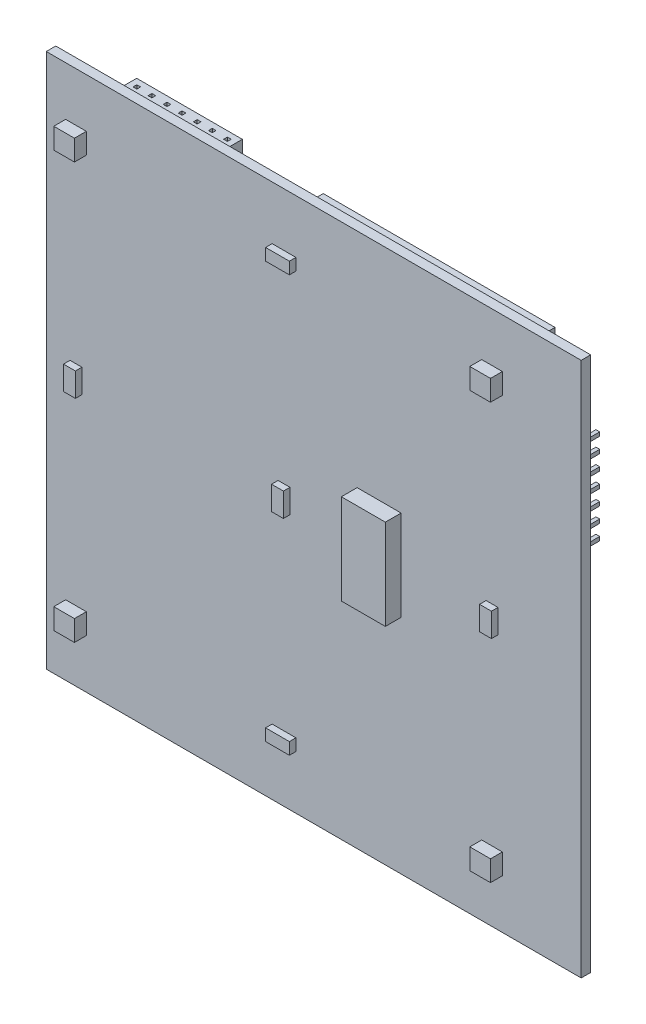
SolidWorks part; units mm, degrees
ref_plane "正面" through (0, 0, 0) normal (0, 0, 1) x (1, 0, 0)
ref_plane "平面" through (0, 0, 0) normal (0, 1, 0) x (1, 0, 0)
ref_plane "右側面" through (0, 0, 0) normal (1, 0, 0) x (0, 0, -1)
sketch "ｽｹｯﾁ1" plane through (0, 0, 0) normal (0, 0, 1) x (1, 0, 0)
  line L0 (-45, 0) -> (45, 0) construction
  line L1 (-45, 45) -> (45, 45)
  line L2 (-45, 45) -> (-45, -45)
  line L3 (-45, -45) -> (45, -45)
  line L4 (45, 45) -> (45, -45)
  line L5 (0, -45) -> (0, 45) construction
  point P8 (0, 0)
  dimension "D1" = 90
  dimension "D2" = 90
  dimension "D3" = 0
  dimension "D4" = 0
extrude "ﾎﾞｽ - 押し出し1" add sketch "ｽｹｯﾁ1" along normal blind 1.6
sketch "ｽｹｯﾁ4" plane through (0, 0, 0) normal (0, 0, -1) x (-1, 0, 0)
  line L0 (-45, -45) -> (-45, 45) construction
  line L1 (-23.89, -36.1) -> (-6.11, -36.1)
  line L2 (-23.89, -36.1) -> (-23.89, -44.6)
  line L3 (-23.89, -44.6) -> (-6.11, -44.6)
  line L4 (-6.11, -36.1) -> (-6.11, -44.6)
  line L6 (45, 45) -> (45, -45) construction
  line L8 (-38.85, 26.89) -> (-36.35, 26.89)
  line L9 (-38.85, 26.89) -> (-38.85, 9.11)
  line L10 (-38.85, 9.11) -> (-36.35, 9.11)
  line L11 (-36.35, 26.89) -> (-36.35, 9.11)
  line L12 (16.11, 44.6) -> (33.89, 44.6)
  line L13 (16.11, 44.6) -> (16.11, 36.1)
  line L14 (16.11, 36.1) -> (33.89, 36.1)
  line L15 (33.89, 44.6) -> (33.89, 36.1)
  line L16 (-45, 45) -> (45, 45) construction
  line L17 (45, -45) -> (-45, -45) construction
  line L18 (36.1, 26.89) -> (44.6, 26.89)
  line L19 (36.1, 26.89) -> (36.1, 9.11)
  line L20 (36.1, 9.11) -> (44.6, 9.11)
  line L21 (44.6, 26.89) -> (44.6, 9.11)
  point P6 (25, 44.6)
  point P7 (-15, -44.6)
  point P14 (-38.85, 18)
  point P15 (-37.6, 9.11)
  point P25 (44.6, 18)
  dimension "D2" = 8.5
  dimension "D3" = 8.5
  dimension "D4" = 17.78
  dimension "D5" = 2.5
  dimension "D6" = 17.78
  dimension "D7" = 27
  dimension "D8" = 7.4
  dimension "D9" = 20
  dimension "D10" = 30
  dimension "D11" = 0.4
  dimension "D12" = 17.78
  dimension "D13" = 17.78
  dimension "D14" = 0.4
  dimension "D15" = 27
  dimension "D16" = 8.5
  dimension "D17" = 0.4
extrude "ﾎﾞｽ - 押し出し2" add sketch "ｽｹｯﾁ4" along normal blind 2.5
sketch "ｽｹｯﾁ5" plane through (0, 0, -2.5) normal (0, 0, -1) x (-1, 0, 0)
  line L8 (-38.85, 9.11) -> (-36.35, 9.11) construction
  line L33 (-37.92, 18.32) -> (-37.28, 18.32)
  line L34 (-37.92, 18.32) -> (-37.92, 17.68)
  line L35 (-37.92, 17.68) -> (-37.28, 17.68)
  line L36 (-37.28, 18.32) -> (-37.28, 17.68)
  line L37 (-38.85, 26.89) -> (-38.85, 9.11) construction
  line L39 (-37.92, 15.78) -> (-37.28, 15.78)
  line L40 (-37.92, 15.78) -> (-37.92, 15.14)
  line L41 (-37.92, 15.14) -> (-37.28, 15.14)
  line L42 (-37.28, 15.78) -> (-37.28, 15.14)
  line L45 (-37.92, 13.24) -> (-37.28, 13.24)
  line L46 (-37.92, 13.24) -> (-37.92, 12.6)
  line L47 (-37.92, 12.6) -> (-37.28, 12.6)
  line L48 (-37.28, 13.24) -> (-37.28, 12.6)
  line L49 (-37.92, 10.7) -> (-37.28, 10.7)
  line L50 (-37.92, 10.7) -> (-37.92, 10.06)
  line L51 (-37.92, 10.06) -> (-37.28, 10.06)
  line L52 (-37.28, 10.7) -> (-37.28, 10.06)
  line L53 (-37.92, 20.86) -> (-37.28, 20.86)
  line L54 (-37.92, 20.86) -> (-37.92, 20.22)
  line L55 (-37.92, 20.22) -> (-37.28, 20.22)
  line L56 (-37.28, 20.86) -> (-37.28, 20.22)
  line L57 (-37.92, 23.4) -> (-37.28, 23.4)
  line L58 (-37.92, 23.4) -> (-37.92, 22.76)
  line L59 (-37.92, 22.76) -> (-37.28, 22.76)
  line L60 (-37.28, 23.4) -> (-37.28, 22.76)
  line L61 (-37.92, 25.94) -> (-37.28, 25.94)
  line L62 (-37.92, 25.94) -> (-37.92, 25.3)
  line L63 (-37.92, 25.3) -> (-37.28, 25.3)
  line L64 (-37.28, 25.94) -> (-37.28, 25.3)
  point P47 (-37.6, 17.68)
  point P50 (-37.6, 9.11)
  point P53 (-37.92, 18)
  point P54 (-38.85, 18)
  point P59 (-37.28, 15.46)
  point P60 (-37.28, 18)
  point P61 (-37.28, 12.92)
  point P70 (-37.28, 10.38)
  point P83 (-37.28, 20.54)
  point P84 (-37.28, 23.08)
  point P85 (-37.28, 25.62)
  point P179 (-37.6, 10.7)
  point P180 (-37.6, 13.24)
  point P181 (-37.6, 15.78)
  point P182 (-37.6, 18.32)
  point P183 (-37.6, 20.86)
  point P184 (-37.6, 23.4)
  point P185 (-37.6, 25.94)
  dimension "D21" = 0.64
  dimension "D22" = 0.64
  dimension "D23" = 0.64
  dimension "D24" = 0.64
  dimension "D25" = 2.54
  dimension "D26" = 0.64
  dimension "D27" = 2.54
  dimension "D28" = 0.64
  dimension "D29" = 2.54
  dimension "D30" = 0.64
  dimension "D31" = 0.64
  dimension "D32" = 0.64
  dimension "D33" = 0.64
  dimension "D34" = 2.54
  dimension "D35" = 2.54
  dimension "D36" = 0.64
  dimension "D37" = 0.64
  dimension "D38" = 0.64
  dimension "D39" = 2.54
  dimension "D40" = 0.64
extrude "ﾎﾞｽ - 押し出し3" add sketch "ｽｹｯﾁ5" along normal blind 6.1
sketch "ｽｹｯﾁ6" plane through (0, 0, 1.6) normal (0, 0, 1) x (1, 0, 0)
  line L0 (-45, -45) -> (45, -45) construction
  line L1 (-41.74, -33.26) -> (-38.26, -33.26)
  line L2 (-41.74, -33.26) -> (-41.74, -36.74)
  line L3 (-41.74, -36.74) -> (-38.26, -36.74)
  line L4 (-38.26, -33.26) -> (-38.26, -36.74)
  line L5 (-45, 45) -> (-45, -45) construction
  line L6 (45, 45) -> (-45, 45) construction
  line L7 (-41.74, 36.74) -> (-38.26, 36.74)
  line L8 (-41.74, 36.74) -> (-41.74, 33.26)
  line L9 (-41.74, 33.26) -> (-38.26, 33.26)
  line L10 (-38.26, 36.74) -> (-38.26, 33.26)
  line L11 (45, -45) -> (45, 45) construction
  line L12 (28.26, -33.26) -> (31.74, -33.26)
  line L13 (28.26, -33.26) -> (28.26, -36.74)
  line L14 (28.26, -36.74) -> (31.74, -36.74)
  line L15 (31.74, -33.26) -> (31.74, -36.74)
  line L17 (28.26, 36.74) -> (31.74, 36.74)
  line L18 (28.26, 36.74) -> (28.26, 33.26)
  line L19 (28.26, 33.26) -> (31.74, 33.26)
  line L20 (31.74, 36.74) -> (31.74, 33.26)
  point P4 (-41.74, -35)
  point P7 (-40, -36.74)
  point P14 (-41.74, 35)
  point P17 (-40, 36.74)
  point P22 (30, -36.74)
  point P25 (31.74, -35)
  point P30 (30, 36.74)
  point P31 (31.74, 35)
  dimension "D1" = 3.48
  dimension "D2" = 3.48
  dimension "D3" = 10
  dimension "D4" = 5
  dimension "D5" = 3.48
  dimension "D6" = 3.48
  dimension "D7" = 10
  dimension "D8" = 5
  dimension "D9" = 15
  dimension "D10" = 10
  dimension "D11" = 3.48
  dimension "D12" = 3.48
  dimension "D13" = 15
  dimension "D14" = 10
  dimension "D15" = 3.48
  dimension "D16" = 3.48
extrude "ﾎﾞｽ - 押し出し4" add sketch "ｽｹｯﾁ6" along normal blind 2
sketch "ｽｹｯﾁ7" plane through (0, 0, 1.6) normal (0, 0, 1) x (1, 0, 0)
  line L0 (-45, -45) -> (45, -45) construction
  line L1 (-41, 2) -> (-39, 2)
  line L2 (-41, 2) -> (-41, -2)
  line L3 (-41, -2) -> (-39, -2)
  line L4 (-39, 2) -> (-39, -2)
  line L5 (-45, 45) -> (-45, -45) construction
  line L6 (45, -45) -> (45, 45) construction
  line L7 (29, 2) -> (31, 2)
  line L8 (29, 2) -> (29, -2)
  line L9 (29, -2) -> (31, -2)
  line L10 (31, 2) -> (31, -2)
  line L11 (45, 45) -> (-45, 45) construction
  line L12 (-7, 36) -> (-3, 36)
  line L13 (-7, 36) -> (-7, 34)
  line L14 (-7, 34) -> (-3, 34)
  line L15 (-3, 36) -> (-3, 34)
  line L17 (-7, -34) -> (-3, -34)
  line L18 (-7, -34) -> (-7, -36)
  line L19 (-7, -36) -> (-3, -36)
  line L20 (-3, -34) -> (-3, -36)
  line L21 (-6, 2) -> (-4, 2)
  line L22 (-6, 2) -> (-6, -2)
  line L23 (-6, -2) -> (-4, -2)
  line L24 (-4, 2) -> (-4, -2)
  point P4 (-41, 0)
  point P7 (-40, -2)
  point P14 (30, 2)
  point P17 (31, 0)
  point P22 (-7, 35)
  point P25 (-5, 36)
  point P30 (-7, -35)
  point P31 (-5, -36)
  point P36 (-4, 0)
  point P37 (29, 0)
  point P38 (-5, 34)
  point P39 (-5, 2)
  dimension "D1" = 4
  dimension "D2" = 2
  dimension "D3" = 45
  dimension "D4" = 5
  dimension "D5" = 4
  dimension "D6" = 2
  dimension "D7" = 15
  dimension "D8" = 45
  dimension "D9" = 4
  dimension "D10" = 2
  dimension "D11" = 10
  dimension "D12" = 40
  dimension "D13" = 4
  dimension "D14" = 2
  dimension "D15" = 10
  dimension "D16" = 40
  dimension "D17" = 4
  dimension "D18" = 2
extrude "ﾎﾞｽ - 押し出し5" add sketch "ｽｹｯﾁ7" along normal blind 1.1
sketch "ｽｹｯﾁ8" plane through (0, 0, 1.6) normal (0, 0, 1) x (1, 0, 0)
  line L1 (7.3, 7.6) -> (14.7, 7.6)
  line L2 (7.3, 7.6) -> (7.3, -7.6)
  line L3 (7.3, -7.6) -> (14.7, -7.6)
  line L4 (14.7, 7.6) -> (14.7, -7.6)
  line L5 (-45, 45) -> (-45, -45) construction
  point P4 (7.3, 0)
  point P11 (-45, 0)
  point P12 (11, 7.6)
  dimension "D1" = 15.2
  dimension "D2" = 7.4
  dimension "D3" = 56
extrude "ﾎﾞｽ - 押し出し6" add sketch "ｽｹｯﾁ8" along normal blind 2.65
sketch "ｽｹｯﾁ9" plane through (0, -44.6, 0) normal (0, -1, 0) x (1, 0, 0)
  line L1 (14.68, -0.93) -> (15.32, -0.93)
  line L2 (14.68, -0.93) -> (14.68, -1.57)
  line L3 (14.68, -1.57) -> (15.32, -1.57)
  line L4 (15.32, -0.93) -> (15.32, -1.57)
  line L5 (6.11, -2.5) -> (6.11, 0) construction
  line L6 (6.11, -1.25) -> (23.89, -1.25) construction
  line L7 (23.89, -2.5) -> (23.89, 0) construction
  line L8 (23.89, -2.5) -> (6.11, -2.5) construction
  line L10 (15, -2.5) -> (15, 0) construction
  line L11 (23.89, 0) -> (6.11, 0) construction
  line L13 (12.14, -0.93) -> (12.78, -0.93)
  line L14 (12.14, -0.93) -> (12.14, -1.57)
  line L15 (12.14, -1.57) -> (12.78, -1.57)
  line L16 (12.78, -0.93) -> (12.78, -1.57)
  line L17 (9.6, -0.93) -> (10.24, -0.93)
  line L18 (9.6, -0.93) -> (9.6, -1.57)
  line L19 (9.6, -1.57) -> (10.24, -1.57)
  line L20 (10.24, -0.93) -> (10.24, -1.57)
  line L21 (7.06, -0.93) -> (7.7, -0.93)
  line L22 (7.06, -0.93) -> (7.06, -1.57)
  line L23 (7.06, -1.57) -> (7.7, -1.57)
  line L24 (7.7, -0.93) -> (7.7, -1.57)
  line L25 (17.22, -0.93) -> (17.86, -0.93)
  line L26 (17.22, -0.93) -> (17.22, -1.57)
  line L27 (17.22, -1.57) -> (17.86, -1.57)
  line L28 (17.86, -0.93) -> (17.86, -1.57)
  line L29 (19.76, -0.93) -> (20.4, -0.93)
  line L30 (19.76, -0.93) -> (19.76, -1.57)
  line L31 (19.76, -1.57) -> (20.4, -1.57)
  line L32 (20.4, -0.93) -> (20.4, -1.57)
  line L33 (22.3, -0.93) -> (22.94, -0.93)
  line L34 (22.3, -0.93) -> (22.3, -1.57)
  line L35 (22.3, -1.57) -> (22.94, -1.57)
  line L36 (22.94, -0.93) -> (22.94, -1.57)
  point P10 (15.32, -1.25)
  point P13 (15, -1.57)
  point P42 (12.46, -1.57)
  point P43 (9.92, -1.57)
  point P44 (12.14, -1.25)
  point P46 (9.6, -1.25)
  point P47 (7.06, -1.25)
  point P48 (7.38, -1.57)
  point P49 (17.54, -1.57)
  point P50 (20.08, -1.57)
  point P51 (22.62, -1.57)
  point P52 (17.22, -1.25)
  point P53 (19.76, -1.25)
  point P54 (22.3, -1.25)
  dimension "D1" = 0.64
  dimension "D2" = 0.64
  dimension "D3" = 0.64
  dimension "D4" = 0.64
  dimension "D5" = 0.64
  dimension "D6" = 0.64
  dimension "D7" = 0.64
  dimension "D8" = 0.64
  dimension "D9" = 0.64
  dimension "D10" = 0.64
  dimension "D11" = 0.64
  dimension "D12" = 2.54
  dimension "D13" = 2.54
  dimension "D14" = 2.54
  dimension "D15" = 0.64
  dimension "D16" = 0.64
  dimension "D17" = 0.64
  dimension "D18" = 2.54
  dimension "D19" = 2.54
  dimension "D20" = 2.54
extrude "ｶｯﾄ - 押し出し1" cut sketch "ｽｹｯﾁ9" against normal blind 7.5
sketch "ｽｹｯﾁ10" plane through (-44.6, 0, 0) normal (-1, 0, 0) x (0, 0, 1)
  line L0 (-1.25, 26.89) -> (-1.25, 9.11) construction
  line L1 (-2.5, 26.89) -> (0, 26.89) construction
  line L2 (-2.5, 9.11) -> (0, 9.11) construction
  line L3 (-2.5, 18) -> (0, 18) construction
  line L4 (-2.5, 9.11) -> (-2.5, 26.89) construction
  line L5 (0, 9.11) -> (0, 26.89) construction
  line L7 (-1.57, 18.32) -> (-0.93, 18.32)
  line L8 (-1.57, 18.32) -> (-1.57, 17.68)
  line L9 (-1.57, 17.68) -> (-0.93, 17.68)
  line L10 (-0.93, 18.32) -> (-0.93, 17.68)
  line L11 (-1.57, 25.94) -> (-0.93, 25.94)
  line L12 (-1.57, 25.94) -> (-1.57, 25.3)
  line L13 (-1.57, 25.3) -> (-0.93, 25.3)
  line L14 (-0.93, 25.94) -> (-0.93, 25.3)
  line L15 (-1.57, 23.4) -> (-0.93, 23.4)
  line L16 (-1.57, 23.4) -> (-1.57, 22.76)
  line L17 (-1.57, 22.76) -> (-0.93, 22.76)
  line L18 (-0.93, 23.4) -> (-0.93, 22.76)
  line L19 (-1.57, 20.86) -> (-0.93, 20.86)
  line L20 (-1.57, 20.86) -> (-1.57, 20.22)
  line L21 (-1.57, 20.22) -> (-0.93, 20.22)
  line L22 (-0.93, 20.86) -> (-0.93, 20.22)
  line L23 (-1.57, 15.78) -> (-0.93, 15.78)
  line L24 (-1.57, 15.78) -> (-1.57, 15.14)
  line L25 (-1.57, 15.14) -> (-0.93, 15.14)
  line L26 (-0.93, 15.78) -> (-0.93, 15.14)
  line L27 (-1.57, 13.24) -> (-0.93, 13.24)
  line L28 (-1.57, 13.24) -> (-1.57, 12.6)
  line L29 (-1.57, 12.6) -> (-0.93, 12.6)
  line L30 (-0.93, 13.24) -> (-0.93, 12.6)
  line L31 (-1.57, 10.7) -> (-0.93, 10.7)
  line L32 (-1.57, 10.7) -> (-1.57, 10.06)
  line L33 (-1.57, 10.06) -> (-0.93, 10.06)
  line L34 (-0.93, 10.7) -> (-0.93, 10.06)
  point P16 (-1.25, 18.32)
  point P17 (-1.57, 18)
  point P30 (-1.57, 20.54)
  point P31 (-0.93, 23.08)
  point P32 (-0.93, 20.54)
  point P33 (-0.93, 25.62)
  point P34 (-1.25, 20.86)
  point P35 (-1.25, 23.4)
  point P36 (-1.25, 25.94)
  point P49 (-0.93, 15.46)
  point P50 (-0.93, 12.92)
  point P51 (-0.93, 10.38)
  dimension "D1" = 0.64
  dimension "D2" = 0.64
  dimension "D3" = 0.64
  dimension "D4" = 0.64
  dimension "D5" = 0.64
  dimension "D6" = 2.54
  dimension "D7" = 2.54
  dimension "D8" = 2.54
  dimension "D9" = 0.64
  dimension "D10" = 0.64
  dimension "D11" = 0.64
  dimension "D12" = 0.64
  dimension "D13" = 0.64
  dimension "D14" = 0.64
  dimension "D15" = 2.54
  dimension "D16" = 2.54
  dimension "D17" = 2.54
  dimension "D18" = 0.64
  dimension "D19" = 0.64
  dimension "D20" = 0.64
extrude "ｶｯﾄ - 押し出し2" cut sketch "ｽｹｯﾁ10" against normal blind 7.5
sketch "ｽｹｯﾁ11" plane through (0, 44.6, 0) normal (0, 1, 0) x (1, 0, 0)
  line L0 (-33.89, 1.25) -> (-16.11, 1.25) construction
  line L1 (-33.89, 2.5) -> (-33.89, 0) construction
  line L2 (-16.11, 2.5) -> (-16.11, 0) construction
  line L3 (-25, 2.5) -> (-25, 0) construction
  line L4 (-33.89, 2.5) -> (-16.11, 2.5) construction
  line L5 (45, 0) -> (-45, 0) construction
  line L7 (-25.32, 1.57) -> (-24.68, 1.57)
  line L8 (-25.32, 1.57) -> (-25.32, 0.93)
  line L9 (-25.32, 0.93) -> (-24.68, 0.93)
  line L10 (-24.68, 1.57) -> (-24.68, 0.93)
  line L11 (-32.94, 1.57) -> (-32.3, 1.57)
  line L12 (-32.94, 1.57) -> (-32.94, 0.93)
  line L13 (-32.94, 0.93) -> (-32.3, 0.93)
  line L14 (-32.3, 1.57) -> (-32.3, 0.93)
  line L15 (-30.4, 1.57) -> (-29.76, 1.57)
  line L16 (-30.4, 1.57) -> (-30.4, 0.93)
  line L17 (-30.4, 0.93) -> (-29.76, 0.93)
  line L18 (-29.76, 1.57) -> (-29.76, 0.93)
  line L19 (-27.86, 1.57) -> (-27.22, 1.57)
  line L20 (-27.86, 1.57) -> (-27.86, 0.93)
  line L21 (-27.86, 0.93) -> (-27.22, 0.93)
  line L22 (-27.22, 1.57) -> (-27.22, 0.93)
  line L23 (-22.78, 1.57) -> (-22.14, 1.57)
  line L24 (-22.78, 1.57) -> (-22.78, 0.93)
  line L25 (-22.78, 0.93) -> (-22.14, 0.93)
  line L26 (-22.14, 1.57) -> (-22.14, 0.93)
  line L27 (-20.24, 1.57) -> (-19.6, 1.57)
  line L28 (-20.24, 1.57) -> (-20.24, 0.93)
  line L29 (-20.24, 0.93) -> (-19.6, 0.93)
  line L30 (-19.6, 1.57) -> (-19.6, 0.93)
  line L31 (-17.7, 1.57) -> (-17.06, 1.57)
  line L32 (-17.7, 1.57) -> (-17.7, 0.93)
  line L33 (-17.7, 0.93) -> (-17.06, 0.93)
  line L34 (-17.06, 1.57) -> (-17.06, 0.93)
  point P16 (-25, 0.93)
  point P17 (-24.68, 1.25)
  point P42 (-27.54, 1.57)
  point P43 (-30.08, 1.57)
  point P44 (-32.62, 1.57)
  point P45 (-32.94, 1.25)
  point P46 (-30.4, 1.25)
  point P47 (-27.86, 1.25)
  point P48 (-22.46, 1.57)
  point P49 (-19.92, 1.57)
  point P50 (-17.38, 1.57)
  point P52 (-22.78, 1.25)
  point P53 (-20.24, 1.25)
  point P54 (-17.7, 1.25)
  dimension "D1" = 0.64
  dimension "D2" = 0.64
  dimension "D3" = 0.64
  dimension "D4" = 0.64
  dimension "D5" = 0.64
  dimension "D6" = 2.54
  dimension "D7" = 2.54
  dimension "D8" = 2.54
  dimension "D9" = 0.64
  dimension "D10" = 0.64
  dimension "D11" = 0.64
  dimension "D12" = 0.64
  dimension "D13" = 0.64
  dimension "D14" = 0.64
  dimension "D15" = 0.64
  dimension "D16" = 0.64
  dimension "D17" = 0.64
  dimension "D18" = 2.54
  dimension "D19" = 2.54
  dimension "D20" = 2.54
extrude "ｶｯﾄ - 押し出し3" cut sketch "ｽｹｯﾁ11" against normal blind 7.5
sketch "ｽｹｯﾁ12" plane through (0, 0, 0) normal (0, 0, -1) x (-1, 0, 0)
  line L7 (45, 45) -> (45, -45) construction
  line L8 (-45, 45) -> (45, 45) construction
  line L9 (45, -45) -> (-45, -45) construction
  line L16 (-45, -45) -> (-45, 45) construction
  line L24 (-23, 30) -> (-24, 31.7321)
  line L25 (-24, 31.7321) -> (-26, 31.7321)
  line L26 (-26, 31.7321) -> (-27, 30)
  line L27 (-27, 30) -> (-26, 28.2679)
  line L28 (-26, 28.2679) -> (-24, 28.2679)
  line L29 (-24, 28.2679) -> (-23, 30)
  line L30 (37, 30) -> (36, 31.7321)
  line L31 (36, 31.7321) -> (34, 31.7321)
  line L32 (34, 31.7321) -> (33, 30)
  line L33 (33, 30) -> (34, 28.2679)
  line L34 (34, 28.2679) -> (36, 28.2679)
  line L35 (36, 28.2679) -> (37, 30)
  line L36 (37, -30) -> (36, -28.2679)
  line L37 (36, -28.2679) -> (34, -28.2679)
  line L38 (34, -28.2679) -> (33, -30)
  line L39 (33, -30) -> (34, -31.7321)
  line L40 (34, -31.7321) -> (36, -31.7321)
  line L41 (36, -31.7321) -> (37, -30)
  line L42 (-23, -30) -> (-24, -28.2679)
  line L43 (-24, -28.2679) -> (-26, -28.2679)
  line L44 (-26, -28.2679) -> (-27, -30)
  line L45 (-27, -30) -> (-26, -31.7321)
  line L46 (-26, -31.7321) -> (-24, -31.7321)
  line L47 (-24, -31.7321) -> (-23, -30)
  circle A0 centre (35, 30) radius 2 construction
  circle A1 centre (35, -30) radius 2 construction
  circle A2 centre (-25, -30) radius 2 construction
  circle A3 centre (-25, 30) radius 2 construction
  dimension "D1" = 10
  dimension "D2" = 15
  dimension "D3" = 15
  dimension "D4" = 10
  dimension "D5" = 15
  dimension "D6" = 20
  dimension "D7" = 20
  dimension "D8" = 15
extrude "ﾎﾞｽ - 押し出し7" add sketch "ｽｹｯﾁ12" along normal blind 3
sketch "ｽｹｯﾁ13" plane through (0, 0, -3) normal (0, 0, -1) x (-1, 0, 0)
  line L0 (-34, 41) -> (-34, 0)
  line L1 (-34, 0) -> (-36, 0)
  line L2 (-36, 0) -> (-36, -39)
  line L3 (-36, -39) -> (5, -39)
  line L4 (5, -39) -> (5, -41)
  line L5 (5, -41) -> (44, -41)
  line L6 (44, -41) -> (44, 0)
  line L7 (44, 0) -> (46, 0)
  line L8 (46, 0) -> (46, 39)
  line L9 (46, 39) -> (5, 39)
  line L10 (5, 39) -> (5, 41)
  line L11 (5, 41) -> (-34, 41)
  line L12 (5, -57.6044) -> (5, 50.3983) construction
  line L13 (45, 45) -> (45, -45) construction
  line L14 (-24, 31.7321) -> (-26, 31.7321) construction
  line L15 (-24, -28.2679) -> (-26, -28.2679) construction
  line L16 (36, -28.2679) -> (34, -28.2679) construction
  line L18 (36, 31.7321) -> (34, 31.7321) construction
  circle A0 centre (-25, 30) radius 1
  circle A1 centre (-25, -30) radius 1
  circle A2 centre (35, -30) radius 1
  circle A3 centre (35, 30) radius 1
  point P4 (0, 0)
  point P17 (0, 0)
  point P26 (-25, 31.7321)
  point P30 (-25, -28.2679)
  point P34 (0, 0)
  point P35 (0, 0)
  point P38 (35, -28.2679)
  point P44 (21.567, 30.6023)
  point P45 (0, 0)
  point P46 (35, 31.7321)
  dimension "D1" = 41
  dimension "D2" = 39
  dimension "D3" = 41
  dimension "D4" = 39
  dimension "D5" = 41
  dimension "D6" = 39
  dimension "D7" = 41
  dimension "D8" = 39
  dimension "D9" = 40
extrude "ﾎﾞｽ - 押し出し8" add sketch "ｽｹｯﾁ13" along normal blind 2
